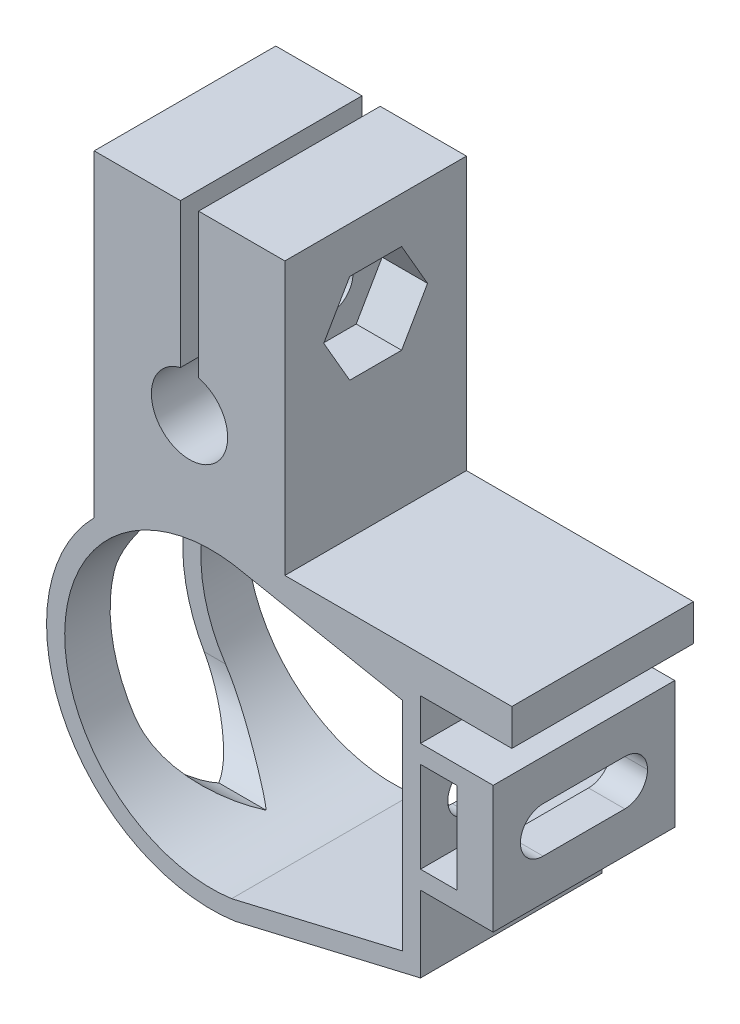
SolidWorks part; units mm, degrees
ref_plane "Alzado" through (0, 0, 0) normal (0, 0, 1) x (1, 0, 0)
ref_plane "Planta" through (0, 0, 0) normal (0, 1, 0) x (1, 0, 0)
ref_plane "Vista lateral" through (0, 0, 0) normal (1, 0, 0) x (0, 0, -1)
sketch "Croquis2" plane through (0, 0, 0) normal (0, 0, 1) x (1, 0, 0)
  line L0 (-51.9511, -1.694) -> (-49.9511, -1.694)
  line L1 (-49.9511, -1.694) -> (-51.9511, -1.694)
  line L2 (-1.9511, -10.694) -> (-1.9511, -41.694)
  line L3 (-1.9511, -41.694) -> (-51.9511, -41.694) construction
  line L4 (-51.9511, -1.694) -> (-51.9511, -41.694) construction
  line L5 (-49.9511, -1.694) -> (-49.9511, -11.294)
  line L6 (-49.9511, -11.294) -> (-36.9511, -11.294)
  line L7 (-36.9511, -11.294) -> (-36.9511, -9.294)
  line L8 (-36.9511, -9.294) -> (-31.9511, -9.294)
  line L9 (-31.9511, -9.294) -> (-31.9511, -11.994)
  line L10 (-31.9511, -11.994) -> (-17.3111, -11.994)
  line L11 (-17.3111, -11.994) -> (-17.3111, -7.694)
  line L12 (-17.3111, -7.694) -> (-24.3111, -7.694)
  line L13 (-24.3111, -7.694) -> (-24.3111, -4.694)
  line L14 (-24.3111, -4.694) -> (-14.3111, -4.694)
  line L15 (-14.3111, -4.694) -> (-14.3111, -10.694)
  line L16 (-14.3111, -10.694) -> (-1.9511, -10.694)
  line L17 (-1.9511, -41.694) -> (-4.5642, -41.694)
  line L18 (-4.5642, -41.694) -> (-4.5642, -19.454)
  line L19 (-4.5642, -19.454) -> (-22.3242, -19.454) construction
  line L20 (-22.3242, -41.694) -> (-22.3242, -15.394) construction
  line L21 (-4.5642, -19.454) -> (-22.3242, -15.394)
  line L22 (-42.1842, -30.694) -> (-40.1642, -30.694)
  line L23 (-22.3242, -15.394) -> (-26.7442, -15.394) construction
  line L24 (-42.1842, -41.694) -> (-42.1842, -30.694) construction
  line L25 (-40.1642, -41.694) -> (-40.1642, -30.694) construction
  line L26 (-26.7442, -15.394) -> (-26.7442, -15.354)
  line L27 (-22.3242, -15.394) -> (-26.7442, -15.354)
  line L28 (-40.1642, -30.694) -> (-26.7442, -15.354) construction
  arc A0 (-40.1642, -30.694) -> (-26.7442, -15.354) centre (-26.4173, -29.1801) cw
  dimension "D1" = 2
  dimension "D2" = 50
  dimension "D3" = 40
  dimension "D4" = 9.6
  dimension "D5" = 13
  dimension "D6" = 2
  dimension "D7" = 5
  dimension "D8" = 2.7
  dimension "D9" = 14.64
  dimension "D10" = 4.3
  dimension "D11" = 3
  dimension "D12" = 10
  dimension "D13" = 6
  dimension "D14" = 12.36
  dimension "D15" = 22.24
  dimension "D16" = 17.76
  dimension "D17" = 26.3
  dimension "D18" = 35.6
  dimension "D19" = 2.02
  dimension "D20" = 11
  dimension "D21" = 4.42
  dimension "D22" = 0.04
sketch "Croquis3" plane through (0, 0, 0) normal (0, 0, 1) x (1, 0, 0)
  line L195 (-42.0992, 14.245) -> (3.9008, 14.245)
  line L202 (-39.0992, 12.245) -> (0.9008, 12.245)
  line L218 (-8.1572, 2.8211) -> (-26.7313, 6.4418)
  line L219 (-8.1572, 2.8211) -> (-8.1572, -21.0951)
  line L220 (-8.1572, -21.0951) -> (-26.9615, -25.5138)
  line L238 (-6.1572, -22.6796) -> (-26.591, -27.4812)
  line L239 (-6.1572, 4.4689) -> (-6.1572, -22.6796) construction
  line L241 (-6.1572, 4.245) -> (-6.1572, -22.6796)
  line L244 (-39.0992, 12.245) -> (-39.0992, 8.245)
  line L245 (-39.0992, 8.245) -> (0.9008, 8.245)
  line L246 (0.9008, 12.245) -> (0.9008, 8.245)
  line L247 (3.9008, 4.245) -> (3.9008, 14.245)
  line L249 (3.9008, 4.245) -> (-6.1572, 4.245)
  line L250 (-42.0992, 3.245) -> (-42.0992, 14.245)
  line L277 (-6.1572, 4.4689) -> (-26.3861, 8.4121) construction
  arc A14 (-26.9615, -25.5138) -> (-26.7313, 6.4418) centre (-29.1957, -9.5191) cw
  arc A17 (-26.591, -27.4812) -> (-42.0992, 3.245) centre (-29.1957, -9.5191) cw
  arc A21 (-26.591, -27.4812) -> (-26.3861, 8.4121) centre (-29.1957, -9.5191) cw construction
  point P4 (0, 0)
  dimension "D18" = 18.8042
  dimension "D15" = 18.574
  dimension "D3" = 46
  dimension "D10" = 4
  dimension "D29" = 16.15
  dimension "D4" = 3
  dimension "D6" = 3
  dimension "D9" = 2
  dimension "D11" = 10
  dimension "D21" = 23.9161
extrude "Saliente-Extruir1" add sketch "Croquis3" along normal blind 20 contours L241 L238 A17 L250 L195 L247 L249 | A14 L218 L219 L220 | L244 L202 L246 L245
sketch "Croquis11" plane through (0, 0, 0) normal (0, 0, -1) x (-1, 0, 0)
  line L2 (-1.8428, -14.3028) -> (-1.8428, -0.3028)
  line L3 (-1.8428, -0.3028) -> (6.1572, -0.3028)
  line L4 (6.1572, -0.3028) -> (6.1572, -2.3028)
  line L5 (6.1572, -2.3028) -> (2.1572, -2.3028)
  line L6 (2.1572, -2.3028) -> (2.1572, -12.3028)
  line L7 (2.1572, -12.3028) -> (6.1572, -12.3028)
  line L8 (6.1572, -12.3028) -> (6.1572, -14.3028)
  line L9 (-1.8428, -14.3028) -> (6.1572, -14.3028)
  line L14 (2.1572, -7.3028) -> (3.8938, -7.3028) construction
  dimension "D1" = 8
  dimension "D2" = 2
  dimension "D3" = 2
  dimension "D4" = 14
  dimension "D5" = 4
extrude "Saliente-Extruir2" add sketch "Croquis11" along direction (0, 0, -1) on the side against the normal up to surface (20 mm away) contours L9 L8 L7 L6 L5 L4 L3 L2 up to face at (-18.0509, -2.2164, 20)
sketch "Croquis12" plane through (1.8428, 0, 0) normal (1, 0, 0) x (0, 0, -1)
  line L0 (-20, -0.3028) -> (0, -0.3028) construction
  line L1 (-20, -0.3028) -> (-20, -14.3028) construction
  line L3 (0, -14.3028) -> (0, -0.3028) construction
  line L5 (-17, -9.8028) -> (-3, -9.8028)
  line L8 (-3, -4.8028) -> (-17, -4.8028)
  line L9 (-17, -4.8028) -> (-17, -9.8028)
  line L11 (-3, -9.8028) -> (-3, -4.8028)
  dimension "D1" = 3
  dimension "D2" = 3
  dimension "D3" = 5
  dimension "D4" = 4.5
extrude "Cortar-Extruir12" cut sketch "Croquis12" against normal up to surface (10 mm away) contours L11 L8 L9 L5 up to face at (-8.1572, -9.137, 10)
fillet "Redondeo1" radius 2.5 8 edges at (-0.1572, -4.8028, 3) (-0.1572, -4.8028, 17) (-7.1572, -9.8028, 3) (-7.1572, -4.8028, 3) (-7.1572, -9.8028, 17) (-7.1572, -4.8028, 17) (-0.1572, -9.8028, 3) (-0.1572, -9.8028, 17)
ref_plane "Plano1" through (-48.1572, 0, 0) normal (-1, 0, 0) x (0, 0, 1)
sketch "Croquis16" plane through (-48.1572, 0, 0) normal (-1, 0, 0) x (0, 0, 1)
  line L2 (25, 5.2572) -> (25, 1.2572) construction
  line L3 (50, 5.2572) -> (0, 5.2572) construction
  line L13 (5, 1.2572) -> (5, -25.4691)
  line L16 (0, 3.245) -> (0, -27.6691) construction
  line L18 (20, -27.6691) -> (20, 3.245) construction
  line L19 (5, 1.2572) -> (15, 1.2572)
  line L20 (5, 1.2572) -> (5, -25.4691)
  line L21 (5, -25.4691) -> (15, -25.4691)
  line L22 (15, 1.2572) -> (15, -25.4691)
  line L24 (0, -27.6691) -> (20, -27.6691) construction
  point P0 (25, 5.245)
  point P10 (25, -25.4691)
  dimension "D2" = 20
  dimension "D3" = 5
  dimension "D4" = 26.7262
  dimension "D1" = 4
  dimension "D5" = 5
  dimension "D6" = 2.2
extrude "Cortar-Extruir17" cut sketch "Croquis16" against normal up to surface (16.4278 mm away) contours L22 L19 L13 L21 region at (-48.1572, -12.106, 10) up to face at (-36.0958, -9.4694, 10)
fillet "Redondeo2" radius 7 4 edges at (-34.7933, -25.4691, 5) (-34.7933, -25.4691, 15) (-42.5125, 1.2572, 15) (-42.5125, 1.2572, 5)
sketch "Croquis17" plane through (0, 0, 20) normal (0, 0, 1) x (1, 0, 0)
  line L0 (-42.0992, 3.245) -> (-42.0992, 14.245) construction
  line L2 (-39.0992, 8.245) -> (-39.0992, 12.245)
  line L3 (-39.0992, 12.245) -> (0.9008, 12.245)
  line L4 (0.9008, 8.245) -> (0.9008, 12.245)
  line L5 (-42.0992, 8.245) -> (-39.0992, 8.245)
  line L6 (-42.0992, 8.245) -> (-42.0992, 14.245)
  line L7 (-42.0992, 14.245) -> (3.9008, 14.245)
  line L8 (3.9008, 8.245) -> (3.9008, 14.245)
  line L9 (0.9008, 8.245) -> (3.9008, 8.245)
extrude "Cortar-Extruir18" cut sketch "Croquis17" against normal through all
sketch "Croquis19" plane through (0, 8.245, 0) normal (0, 1, 0) x (1, 0, 0)
  line L0 (3.9008, -10) -> (-0.26, -10) construction
  line L1 (-42.0992, 0) -> (-21.0992, 0)
  line L2 (-42.0992, 0) -> (-42.0992, -20)
  line L3 (-42.0992, -20) -> (-21.0992, -20)
  line L4 (-21.0992, 0) -> (-21.0992, -20)
  line L5 (3.9008, 0) -> (3.9008, -20) construction
  point P12 (-21.0992, -10)
  point P13 (0, 0)
  dimension "D1" = 20
  dimension "D2" = 21
  dimension "D3" = 25
extrude "Saliente-Extruir3" add sketch "Croquis19" along normal blind 30
sketch "Croquis20" plane through (0, 0, 20) normal (0, 0, 1) x (1, 0, 0)
  line L0 (-31.5992, 38.245) -> (-31.5992, 23.7661) construction
  line L1 (-42.0992, 38.245) -> (-21.0992, 38.245) construction
  line L2 (-31.5992, 23.7661) -> (-31.5992, 12.7239) construction
  line L4 (-31.5992, 38.245) -> (-30.5992, 38.245)
  line L5 (-30.5992, 38.245) -> (-30.5992, 22.3242)
  line L6 (-31.5992, 38.245) -> (-32.5992, 38.245)
  line L7 (-32.5992, 38.245) -> (-32.5992, 22.3242)
  arc A0 (-32.5992, 22.3242) -> (-30.5992, 22.3242) centre (-31.5992, 18.245) ccw
  dimension "D2" = 4.2
  dimension "D1" = 20
  dimension "D3" = 1
sketch "Croquis21" plane through (-21.0992, 0, 0) normal (1, 0, 0) x (0, 0, -1)
  line L0 (-10, 38.245) -> (-10, 28.245) construction
  line L1 (-20, 38.245) -> (0, 38.245) construction
  circle A0 centre (-10, 28.245) radius 2.5
  dimension "D2" = 5
  dimension "D1" = 10
extrude "Cortar-Extruir20" cut sketch "Croquis21" against normal up to surface (21 mm away) up to face at (-42.0992, 20.745, 10)
sketch "Croquis22" plane through (-42.0992, 0, 0) normal (-1, 0, 0) x (0, 0, 1)
  circle A0 centre (10, 28.245) radius 2.5 construction
  circle A1 centre (10, 28.245) radius 2.5 construction
  circle A2 centre (10, 28.245) radius 4.65
  dimension "D1" = 9.3
extrude "Cortar-Extruir21" cut sketch "Croquis22" against normal blind 5
extrude "Cortar-Extruir22" cut sketch "Croquis20" against normal up to next
sketch "Croquis23" plane through (-21.0992, 0, 0) normal (1, 0, 0) x (0, 0, -1)
  line L0 (-20, 38.245) -> (0, 38.245) construction
  line L7 (-4.2842, 28.245) -> (-7.1421, 33.195)
  line L8 (-7.1421, 33.195) -> (-12.8579, 33.195)
  line L9 (-12.8579, 33.195) -> (-15.7158, 28.245)
  line L10 (-15.7158, 28.245) -> (-12.8579, 23.295)
  line L11 (-12.8579, 23.295) -> (-7.1421, 23.295)
  line L12 (-7.1421, 23.295) -> (-4.2842, 28.245)
  circle A0 centre (-10, 28.245) radius 4.95 construction
  dimension "D1" = 9.9
extrude "Cortar-Extruir23" cut sketch "Croquis23" against normal blind 5
